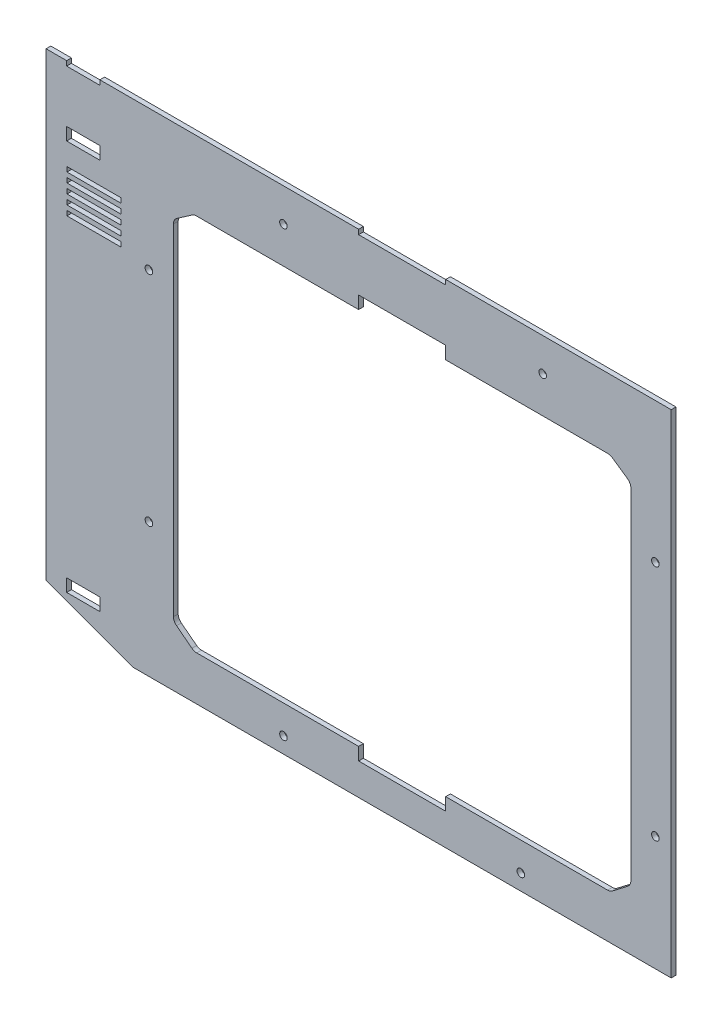
SolidWorks part; units mm, degrees
ref_plane "Piano frontale" through (0, 0, 0) normal (0, 0, 1) x (1, 0, 0)
ref_plane "Piano superiore" through (0, 0, 0) normal (0, 1, 0) x (1, 0, 0)
ref_plane "Piano destro" through (0, 0, 0) normal (1, 0, 0) x (0, 0, -1)
sketch "Schizzo1" plane through (0, 0, 0) normal (0, 0, 1) x (1, 0, 0)
  line L0 (-131.5, -127.5) -> (-144.5, -117.5)
  line L1 (170, -155.5) -> (-170, -155.5)
  line L2 (170, -155.5) -> (170, 155.5)
  line L3 (170, 155.5) -> (-170, 155.5)
  line L4 (-170, -155.5) -> (-170, 155.5)
  line L5 (170, -155.5) -> (-170, 155.5) construction
  line L6 (170, 155.5) -> (-170, -155.5) construction
  line L7 (144.5, -127.5) -> (-144.5, -127.5)
  line L8 (144.5, -127.5) -> (144.5, 111.5)
  line L9 (144.5, 111.5) -> (-144.5, 111.5)
  line L10 (-144.5, -127.5) -> (-144.5, 111.5)
  line L11 (144.5, -127.5) -> (-144.5, 111.5) construction
  line L12 (144.5, 111.5) -> (-144.5, -127.5) construction
  line L13 (131.5, -127.5) -> (144.5, -117.5)
  line L14 (-131.5, 111.5) -> (-144.5, 102.5)
  line L15 (131.5, 111.5) -> (144.5, 102.5)
  line L16 (-170, 134.5) -> (170, 134.5) construction
  line L17 (-160, 155.5) -> (-160, -155.5) construction
  line L18 (160, 155.5) -> (160, -155.5) construction
  line L19 (-170, -145.5) -> (170, -145.5) construction
  line L20 (-239.9413, -8) -> (269.8468, -8) construction
  line L21 (0, 197.8715) -> (0, -197.8715) construction
  line L22 (-239.9413, -83) -> (269.8468, -83) construction
  line L23 (-75, 197.8715) -> (-75, -197.8715) construction
  line L24 (-239.9413, 67) -> (269.8468, 67) construction
  line L25 (75, 197.8715) -> (75, -197.8715) construction
  line L26 (-27.5, -131.5) -> (27.5, -131.5) construction
  line L27 (-170, 155.5) -> (-225, 155.5)
  line L28 (-170, 155.5) -> (-170, -155.5)
  line L29 (-170, -155.5) -> (-225, -155.5)
  line L30 (-225, 155.5) -> (-225, -155.5)
  line L31 (-197.5, -155.5) -> (-197.5, 155.5) construction
  line L32 (-170, 0) -> (-225, 0) construction
  line L33 (-212, 155.5) -> (-191, 155.5)
  line L34 (-212, 155.5) -> (-212, 152.5)
  line L35 (-212, 152.5) -> (-191, 152.5)
  line L36 (-191, 155.5) -> (-191, 152.5)
  line L37 (-201.5, 152.5) -> (-201.5, 155.5) construction
  line L38 (-212, 154) -> (-191, 154) construction
  line L39 (-27.5, 155.5) -> (27.5, 155.5)
  line L40 (-27.5, 155.5) -> (-27.5, 152.5)
  line L41 (-27.5, 152.5) -> (27.5, 152.5)
  line L42 (27.5, 155.5) -> (27.5, 152.5)
  line L43 (0, 152.5) -> (0, 155.5) construction
  line L44 (-27.5, 154) -> (27.5, 154) construction
  line L45 (-27.5, 111.5) -> (27.5, 111.5)
  line L46 (-27.5, 111.5) -> (-27.5, 119.5)
  line L47 (-27.5, 119.5) -> (27.5, 119.5)
  line L48 (27.5, 111.5) -> (27.5, 119.5)
  line L49 (0, 119.5) -> (0, 111.5) construction
  line L50 (-27.5, 115.5) -> (27.5, 115.5) construction
  line L51 (0, -135.5) -> (0, -127.5) construction
  line L52 (27.5, -127.5) -> (27.5, -135.5)
  line L53 (-27.5, -135.5) -> (27.5, -135.5)
  line L54 (-27.5, -127.5) -> (-27.5, -135.5)
  line L55 (-27.5, -127.5) -> (27.5, -127.5)
  line L56 (-212, 155.5) -> (-212, -197.8715) construction
  line L57 (-191, 152.5) -> (-191, -222.383) construction
  line L58 (-170, -155.5) -> (-225, -135.5)
  line L59 (-212, 111.5) -> (-191, 111.5)
  line L60 (-212, 111.5) -> (-212, 119.5)
  line L61 (-212, 119.5) -> (-191, 119.5)
  line L62 (-191, 111.5) -> (-191, 119.5)
  line L63 (-201.5, 119.5) -> (-201.5, 111.5) construction
  line L64 (-212, 115.5) -> (-191, 115.5) construction
  line L65 (-212, -127.5) -> (-191, -127.5)
  line L66 (-212, -127.5) -> (-212, -135.5)
  line L67 (-212, -135.5) -> (-191, -135.5)
  line L68 (-191, -127.5) -> (-191, -135.5)
  line L69 (-201.5, -135.5) -> (-201.5, -127.5) construction
  line L70 (-212, -131.5) -> (-191, -131.5) construction
  circle A0 centre (88.8086, 134.5) radius 2.4
  circle A1 centre (-75, 134.5) radius 2.4
  circle A2 centre (-160, 67) radius 2.4
  circle A3 centre (160, 67) radius 2.4
  circle A4 centre (160, -83) radius 2.4
  circle A5 centre (-160, -70.8211) radius 2.4
  circle A6 centre (-75, -145.5) radius 2.4
  circle A7 centre (75, -145.5) radius 2.4
  point P0 (0, 0)
  point P6 (0, -8)
  point P78 (0, -131.5)
  point P178 (-201.5, 154)
  point P195 (0, 154)
  point P284 (0, 115.5)
  point P341 (-197.5, 0)
  point P480 (-201.5, -131.5)
  point P500 (-201.5, 115.5)
  dimension "D21" = 4.8
  dimension "D1" = 311
  dimension "D2" = 340
  dimension "D3" = 44
  dimension "D4" = 28
  dimension "D5" = 25.5
  dimension "D6" = 25.5
  dimension "D7" = 13
  dimension "D8" = 10
  dimension "D9" = 13
  dimension "D10" = 10
  dimension "D11" = 13
  dimension "D12" = 9
  dimension "D13" = 13
  dimension "D14" = 9
  dimension "D15" = 21
  dimension "D16" = 10
  dimension "D17" = 10
  dimension "D18" = 10
  dimension "D22" = 55
  dimension "D23" = 21
  dimension "D24" = 21
  dimension "D25" = 3
  dimension "D26" = 3
  dimension "D27" = 55
  dimension "D28" = 55
  dimension "D29" = 8
  dimension "D30" = 0
  dimension "D31" = 0
  dimension "D32" = 20
  dimension "D19" = 75
  dimension "D20" = 75
extrude "Estrusione-Estrusione1" add sketch "Schizzo1" along normal blind 3 contours L4 L1 L2 L3 L7 L10 L9 L8 | L10 L7 L0 | L13 L7 L8 | L14 L9 L10 | L9 L15 L8 | L27 L36 L35 L34 L30 L29 L4 L62 L59 L60 L61 L65 L68 L67 L66 region at (-140.1667, -124.1667, 0) region at (-140.1667, 108.5, 0) region at (140.1667, -124.1667, 0) region at (140.1667, 108.5, 0) region at (0, -150.8922, 0) region at (-197.0892, 4.6326, 0)
fillet "Raccordo1" radius 5 8 edges at (-144.5, -117.5, 1.5) (-131.5, -127.5, 1.5) (131.5, -127.5, 1.5) (144.5, -117.5, 1.5) (144.5, 102.5, 1.5) (131.5, 111.5, 1.5) (-131.5, 111.5, 1.5) (-144.5, 102.5, 1.5)
sketch "Schizzo2" plane through (0, 0, 0) normal (0, 0, -1) x (-1, 0, 0)
  line L0 (177.776, 97.6349) -> (211.776, 97.6349)
  line L1 (177.776, 100.6349) -> (211.776, 100.6349)
  line L2 (177.776, 100.6349) -> (177.776, 66.6349)
  line L3 (177.776, 66.6349) -> (211.776, 66.6349)
  line L4 (211.776, 100.6349) -> (211.776, 66.6349)
  line L5 (194.776, 66.6349) -> (194.776, 100.6349) construction
  line L6 (177.776, 83.6349) -> (211.776, 83.6349) construction
  line L7 (177.776, 94.6349) -> (211.776, 94.6349)
  line L8 (177.776, 91.6349) -> (211.776, 91.6349)
  line L9 (177.776, 88.6349) -> (211.776, 88.6349)
  line L10 (177.776, 85.6349) -> (211.776, 85.6349)
  line L11 (177.776, 82.6349) -> (211.776, 82.6349)
  line L12 (177.776, 79.6349) -> (211.776, 79.6349)
  line L13 (177.776, 76.6349) -> (211.776, 76.6349)
  line L14 (177.776, 73.6349) -> (211.776, 73.6349)
  line L15 (177.776, 70.6349) -> (211.776, 70.6349)
  point P228 (194.776, 83.6349)
  dimension "D1" = 34
  dimension "D2" = 34
  dimension "D3" = 3
  dimension "D4" = 3
  dimension "D5" = 3
  dimension "D6" = 8
extrude "Taglio-Estrusione1" cut sketch "Schizzo2" against normal blind 10 contours L2 L7 L4 L0 | L2 L9 L4 L8 | L2 L11 L4 L10 | L2 L13 L4 L12 | L2 L15 L4 L14 region at (-194.776, 96.1349, 0) region at (-194.776, 90.1349, 0) region at (-194.776, 84.1349, 0) region at (-194.776, 78.1349, 0) region at (-194.776, 72.1349, 0)
